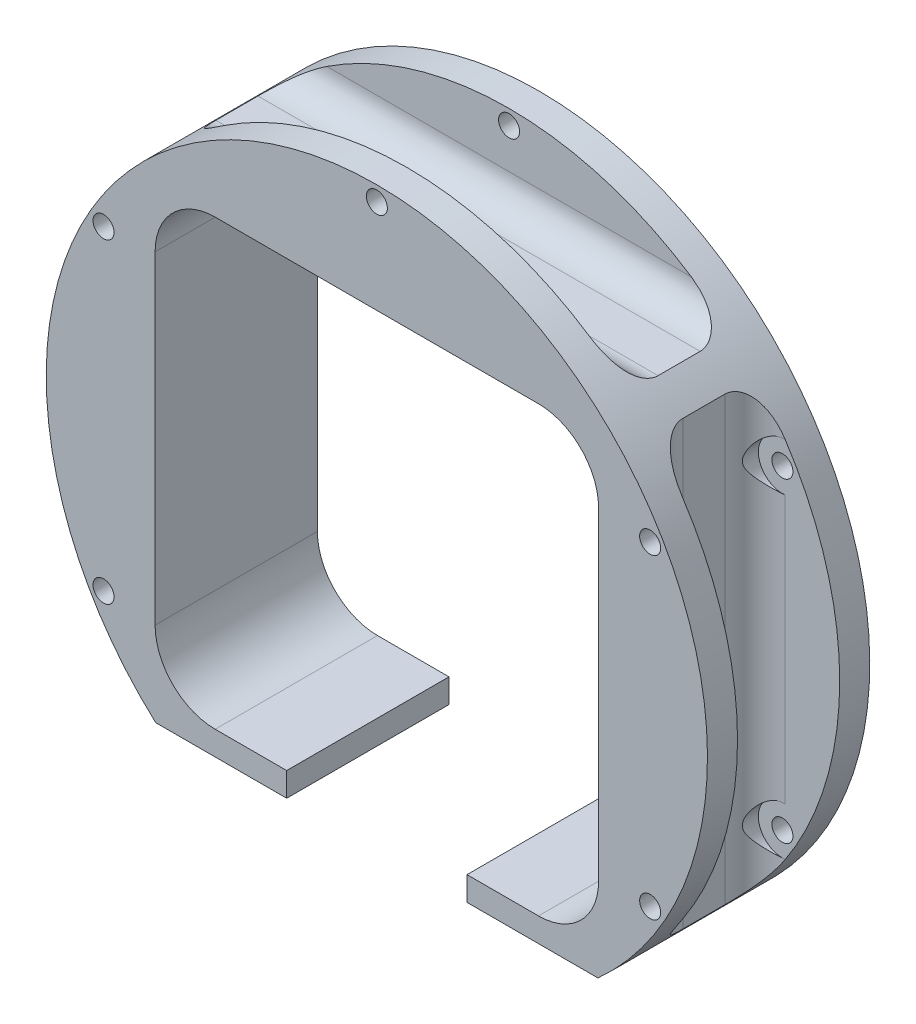
SolidWorks part; units mm, degrees
ref_plane "前视基准面" through (0, 0, 0) normal (0, 0, 1) x (1, 0, 0)
ref_plane "上视基准面" through (0, 0, 0) normal (0, 1, 0) x (1, 0, 0)
ref_plane "右视基准面" through (0, 0, 0) normal (1, 0, 0) x (0, 0, -1)
other "Configuration Table"
sketch "草图2" plane through (0, 0, 0) normal (0, 0, 1) x (1, 0, 0)
  line L0 (-18, 72) -> (18, 24) construction
  line L1 (-38.8909, 86.8909) -> (38.8909, 86.8909)
  line L2 (-38.8909, 86.8909) -> (-38.8909, 9.1091)
  line L3 (-38.8909, 9.1091) -> (38.8909, 9.1091)
  line L4 (38.8909, 86.8909) -> (38.8909, 9.1091)
  line L5 (-38.8909, 86.8909) -> (38.8909, 9.1091) construction
  line L6 (-38.8909, 9.1091) -> (38.8909, 86.8909) construction
  line L7 (-40.8909, 88.8909) -> (40.8909, 88.8909)
  line L8 (40.8909, 88.8909) -> (40.8909, 7.1091)
  line L9 (-40.8909, 7.1091) -> (40.8909, 7.1091)
  line L10 (-40.8909, 88.8909) -> (-40.8909, 7.1091)
  line L11 (-36.8909, 84.8909) -> (36.8909, 84.8909)
  line L12 (36.8909, 84.8909) -> (36.8909, 11.1091)
  line L13 (-36.8909, 11.1091) -> (36.8909, 11.1091)
  line L14 (-36.8909, 84.8909) -> (-36.8909, 11.1091)
  circle A0 centre (0, 48) radius 55
  point P0 (0, 48)
  dimension "D3" = 110
  dimension "D1" = 2
  dimension "D2" = 2
extrude "凸台-拉伸1" add sketch "草图2" along normal blind 22 contours L4 L1 L2 L3 L14 L11 L12 L13 | L2 A0 L10 | L1 A0 L7 | L8 A0 L4 | L3 A0 L9 region at (0, 87.8816, 0) region at (0, 85.7909, 0) region at (-39.8816, 48, 0) region at (39.8816, 48, 0) region at (0, 8.1184, 0)
sketch "草图3" plane through (0, 0, 22) normal (0, 0, 1) x (1, 0, 0)
  line L0 (-36.7823, 7.1091) -> (36.7823, 7.1091) construction
  line L1 (-15, 12.7177) -> (15, 12.7177)
  line L2 (-15, 12.7177) -> (-15, 1.5005)
  line L3 (-15, 1.5005) -> (15, 1.5005)
  line L4 (15, 12.7177) -> (15, 1.5005)
  line L5 (-15, 12.7177) -> (15, 1.5005) construction
  line L6 (-15, 1.5005) -> (15, 12.7177) construction
  point P0 (0, 7.1091)
  dimension "D1" = 11.2172
  dimension "D2" = 30
extrude "切除-拉伸1" cut sketch "草图3" against normal blind 25
fillet "圆角2" radius 10 4 edges at (36.8909, 11.1091, 11) (-36.8909, 11.1091, 11) (-36.8909, 84.8909, 11) (36.8909, 84.8909, 11)
sketch "草图4" plane through (0, 0, 22) normal (0, 0, 1) x (1, 0, 0)
  circle A0 centre (0, 48) radius 55
  circle A1 centre (0, 48) radius 52.5
  circle A2 centre (0, 48) radius 50
  circle A3 centre (0, 100.5) radius 1.5
  circle A4 centre (45.4663, 74.25) radius 1.5
  circle A5 centre (45.4663, 21.75) radius 1.5
  circle A6 centre (0, -4.5) radius 1.5
  circle A7 centre (-45.4663, 21.75) radius 1.5
  circle A8 centre (-45.4663, 74.25) radius 1.5
  point P20 (0, 48)
  line M4 (15, 11.1091) -> (15, 7.1091)
  line M5 (15, 7.1091) -> (36.7823, 7.1091)
  arc M6 (36.7823, 7.1091) -> (40.8909, 11.2177) centre (0, 48) ccw
  line M7 (40.8909, 11.2177) -> (40.8909, 84.7823)
  arc M8 (40.8909, 84.7823) -> (36.7823, 88.8909) centre (0, 48) ccw
  line M9 (36.7823, 88.8909) -> (-36.7823, 88.8909)
  arc M10 (-36.7823, 88.8909) -> (-40.8909, 84.7823) centre (0, 48) ccw
  line M11 (-40.8909, 84.7823) -> (-40.8909, 11.2177)
  arc M12 (-40.8909, 11.2177) -> (-36.7823, 7.1091) centre (0, 48) ccw
  line M13 (-36.7823, 7.1091) -> (-15, 7.1091)
  line M14 (-15, 7.1091) -> (-15, 11.1091)
  line M15 (-15, 11.1091) -> (-26.8909, 11.1091)
  arc M16 (-26.8909, 11.1091) -> (-36.8909, 21.1091) centre (-26.8909, 21.1091) cw
  line M17 (-36.8909, 21.1091) -> (-36.8909, 74.8909)
  arc M18 (-36.8909, 74.8909) -> (-26.8909, 84.8909) centre (-26.8909, 74.8909) cw
  line M19 (-26.8909, 84.8909) -> (26.8909, 84.8909)
  arc M20 (26.8909, 84.8909) -> (36.8909, 74.8909) centre (26.8909, 74.8909) cw
  line M21 (36.8909, 74.8909) -> (36.8909, 21.1091)
  arc M22 (36.8909, 21.1091) -> (26.8909, 11.1091) centre (26.8909, 21.1091) cw
  line M23 (26.8909, 11.1091) -> (15, 11.1091)
  dimension "D1" = 110
  dimension "D2" = 105
  dimension "D3" = 100
  dimension "D4" = 3
  dimension "D5" = 6
extrude "凸台-拉伸2" add sketch "草图4" along normal blind 5 contours A3 A1 A0 M9 | A3 A1 A2 M9 | A1 M7 M8 M9 | A2 A1 M7 M9 | A5 A1 A0 A4 M7 | A5 A1 A4 A2 M7 | A1 M5 M6 M7 | A6 A1 A0 M13 M5 | A6 A1 A2 M5 M13 | A2 A1 M5 M7 | A2 A1 M11 M13 | A1 M11 M12 M13 | A8 A1 A7 A2 M11 | A8 A1 A0 A7 M11 | A2 A1 M9 M11 | A1 M9 M10 M11 | A2 M11 | A2 M9 | A2 M7 M9 M11 M13 M14 M15 M16 M17 M18 M19 M20 M21 M22 M23 M4 M5 | A2 M7 region at (50.6524, 28.5705, 22) region at (37.8682, 85.8682, 22) region at (37.8682, 10.1318, 22) region at (34.8546, 89.6399, 22) region at (36.0561, 84.0561, 22) region at (42.3329, 77.9066, 22) region at (0, -6.2509, 22) region at (36.0561, 11.9439, 22) region at (-37.8682, 85.8682, 22) region at (30.8504, 89.5595, 22) region at (39.7343, 48, 22) region at (44.5646, 48, 22) region at (-37.8682, 10.1318, 22) region at (17.931, -0.6309, 22) region at (-41.6399, 82.8546, 22) region at (-36.0561, 84.0561, 22) region at (0, 92.5646, 22) region at (-36.0561, 11.9439, 22) region at (-41.5596, 78.8504, 22) region at (-44.5646, 48, 22)
sketch "草图5" plane through (0, 0, 27) normal (0, 0, 1) x (1, 0, 0)
  line L0 (-28.7739, 7.1091) -> (-36.7823, 7.1091)
  line L1 (-36.7823, 7.1091) -> (36.7823, 7.1091)
  line L2 (36.7823, 7.1091) -> (11.1253, -32.3806)
  line L3 (11.1253, -32.3806) -> (-38.9208, 2.5325)
  line L4 (-38.9208, 2.5325) -> (-36.7823, 7.1091)
  circle A0 centre (0, 48) radius 55 construction
  circle M1 centre (0, -4.5) radius 1.5
  arc M2 (28.7739, 7.1091) -> (-28.7739, 7.1091) centre (0, 48) cw
  line M3 (-28.7739, 7.1091) -> (-15, 7.1091)
  line M15 (15, 7.1091) -> (28.7739, 7.1091)
  circle M16 centre (0, 48) radius 55
extrude "切除-拉伸2" cut sketch "草图5" against normal through all both and the other way through all contours L4 L3 L2 M16 | L1 L0 M2 M16 M1 | L1 M3 M2 M15 region at (0, -2.7491, 27) region at (0, 3.4354, 27) region at (2.373, -12.2585, 27)
fillet "圆角3" radius 5 3 edges at (40.8909, 48, 22) (-40.8909, 48, 22) (0, 88.8909, 22)
sketch "草图6" plane through (0, 0, 0) normal (0, 0, -1) x (-1, 0, 0)
  line L0 (-36.7823, 7.1091) -> (36.7823, 7.1091)
  line L13 (-36.7823, 7.1091) -> (-15, 7.1091)
  line L14 (-15, 7.1091) -> (-15, 11.1091)
  line L15 (-15, 11.1091) -> (-26.8909, 11.1091)
  line L16 (-36.8909, 21.1091) -> (-36.8909, 74.8909)
  line L17 (-26.8909, 84.8909) -> (26.8909, 84.8909)
  line L18 (36.8909, 74.8909) -> (36.8909, 21.1091)
  line L19 (26.8909, 11.1091) -> (15, 11.1091)
  line L20 (15, 11.1091) -> (15, 7.1091)
  line L21 (15, 7.1091) -> (36.7823, 7.1091)
  line L22 (40.8909, 11.2177) -> (40.8909, 84.7823)
  line L23 (36.7823, 88.8909) -> (-36.7823, 88.8909)
  line L24 (-40.8909, 84.7823) -> (-40.8909, 11.2177)
  line L25 (-36.7823, 7.1091) -> (-15, 7.1091)
  line L26 (-15, 7.1091) -> (-15, 11.1091)
  line L27 (-15, 11.1091) -> (-26.8909, 11.1091)
  line L28 (-36.8909, 21.1091) -> (-36.8909, 74.8909)
  line L29 (-26.8909, 84.8909) -> (26.8909, 84.8909)
  line L30 (36.8909, 74.8909) -> (36.8909, 21.1091)
  line L31 (26.8909, 11.1091) -> (15, 11.1091)
  line L32 (15, 11.1091) -> (15, 7.1091)
  line L33 (15, 7.1091) -> (36.7823, 7.1091)
  line L34 (40.8909, 11.2177) -> (40.8909, 84.7823)
  line L35 (36.7823, 88.8909) -> (-36.7823, 88.8909)
  line L36 (-40.8909, 84.7823) -> (-40.8909, 11.2177)
  arc A0 (-36.7823, 7.1091) -> (36.7823, 7.1091) centre (0, 48) ccw
  circle A1 centre (0, 48) radius 55
  arc A9 (-36.8909, 21.1091) -> (-26.8909, 11.1091) centre (-26.8909, 21.1091) ccw
  arc A10 (-26.8909, 84.8909) -> (-36.8909, 74.8909) centre (-26.8909, 74.8909) ccw
  arc A11 (36.8909, 74.8909) -> (26.8909, 84.8909) centre (26.8909, 74.8909) ccw
  arc A12 (26.8909, 11.1091) -> (36.8909, 21.1091) centre (26.8909, 21.1091) ccw
  arc A13 (36.7823, 7.1091) -> (40.8909, 11.2177) centre (0, 48) ccw
  arc A14 (40.8909, 84.7823) -> (36.7823, 88.8909) centre (0, 48) ccw
  arc A15 (-36.7823, 88.8909) -> (-40.8909, 84.7823) centre (0, 48) ccw
  arc A16 (-40.8909, 11.2177) -> (-36.7823, 7.1091) centre (0, 48) ccw
  arc A17 (-36.8909, 21.1091) -> (-26.8909, 11.1091) centre (-26.8909, 21.1091) ccw
  arc A18 (-26.8909, 84.8909) -> (-36.8909, 74.8909) centre (-26.8909, 74.8909) ccw
  arc A19 (36.8909, 74.8909) -> (26.8909, 84.8909) centre (26.8909, 74.8909) ccw
  arc A20 (26.8909, 11.1091) -> (36.8909, 21.1091) centre (26.8909, 21.1091) ccw
  arc A21 (36.7823, 7.1091) -> (40.8909, 11.2177) centre (0, 48) ccw
  arc A22 (40.8909, 84.7823) -> (36.7823, 88.8909) centre (0, 48) ccw
  arc A23 (-36.7823, 88.8909) -> (-40.8909, 84.7823) centre (0, 48) ccw
  arc A24 (-40.8909, 11.2177) -> (-36.7823, 7.1091) centre (0, 48) ccw
  line M36 (40.8909, 11.2177) -> (40.8909, 84.7823)
  line M38 (36.7823, 88.8909) -> (-36.7823, 88.8909)
  line M40 (-40.8909, 84.7823) -> (-40.8909, 11.2177)
  dimension "D1" = 0
  dimension "D2" = 110
extrude "凸台-拉伸3" add sketch "草图6" against normal blind 5 contours A1 M40 | A1 M38 | A1 M36 region at (46.6016, 48, 0) region at (-46.6016, 48, 0) region at (0, 94.6016, 0)
sketch "草图7" plane through (0, 0, 5) normal (0, 0, 1) x (1, 0, 0)
  circle A1 centre (45.4663, 21.75) radius 1.5
  circle A2 centre (45.4663, 21.75) radius 1.5
  circle A3 centre (45.4663, 74.25) radius 1.5
  circle A4 centre (45.4663, 74.25) radius 1.5
  circle A5 centre (-45.4663, 74.25) radius 1.5
  circle A6 centre (-45.4663, 74.25) radius 1.5
  circle A7 centre (-45.4663, 21.75) radius 1.5
  circle A8 centre (-45.4663, 21.75) radius 1.5
  circle A9 centre (0, 100.5) radius 1.5
  circle A10 centre (0, 100.5) radius 1.5
  dimension "D1" = 0
  dimension "D2" = 0
  dimension "D3" = 0
  dimension "D4" = 0
  dimension "D5" = 0
extrude "切除-拉伸3" cut sketch "草图7" against normal blind 5
fillet "圆角4" radius 5 3 edges at (-40.8909, 48, 5) (0, 88.8909, 5) (40.8909, 48, 5)
ref_plane "基准面1" through (0, 0, 13.5) normal (0, 0, -1) x (-1, 0, 0)
sketch "草图8" plane through (0, 0, 13.5) normal (0, 0, -1) x (-1, 0, 0)
  circle A0 centre (-45.4663, 74.25) radius 4
  circle A1 centre (-45.4663, 21.75) radius 4
  circle A2 centre (45.4663, 21.75) radius 4
  circle A3 centre (45.4663, 74.25) radius 4
  dimension "D1" = 8
  dimension "D2" = 8
  dimension "D3" = 8
  dimension "D4" = 8
extrude "切除-拉伸4" cut sketch "草图8" against normal blind 8.5 and the other way blind 8.5
sketch "草图9" plane through (0, 0, 0) normal (0, 0, -1) x (-1, 0, 0)
  circle A0 centre (-45.4663, 74.25) radius 1.75
  circle A1 centre (45.4663, 21.75) radius 1.5
  circle A2 centre (45.4663, 21.75) radius 1.5
  circle A3 centre (0, 100.5) radius 1.5
  circle A4 centre (0, 100.5) radius 1.5
  circle A5 centre (-45.4663, 21.75) radius 1.5
  circle A6 centre (-45.4663, 21.75) radius 1.5
  circle A7 centre (45.4663, 74.25) radius 1.5
  circle A8 centre (45.4663, 74.25) radius 1.5
  circle A9 centre (-45.4663, 74.25) radius 1.5
  circle A10 centre (-45.4663, 74.25) radius 1.5
  circle A11 centre (0, 100.5) radius 1.75
  circle A12 centre (45.4663, 74.25) radius 1.75
  circle A13 centre (45.4663, 21.75) radius 1.75
  circle A14 centre (-45.4663, 21.75) radius 1.75
  dimension "D1" = 0
  dimension "D2" = 0
  dimension "D3" = 0
  dimension "D4" = 0
  dimension "D5" = 0
  dimension "D6" = 0.25
extrude "切除-拉伸5" cut sketch "草图9" against normal through all
